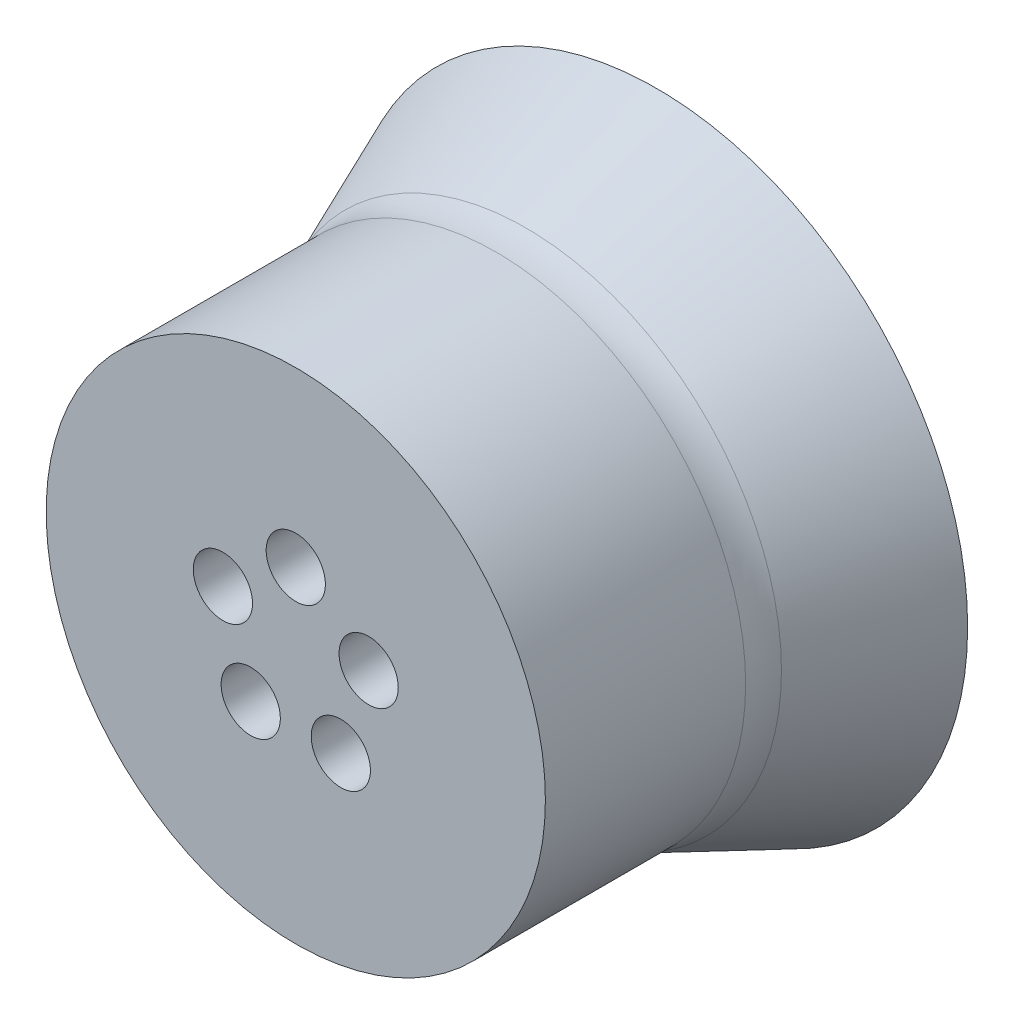
SolidWorks part; units mm, degrees
ref_plane "Front Plane" through (0, 0, 0) normal (0, 0, 1) x (1, 0, 0)
ref_plane "Top Plane" through (0, 0, 0) normal (0, 1, 0) x (1, 0, 0)
ref_plane "Right Plane" through (0, 0, 0) normal (1, 0, 0) x (0, 0, -1)
sketch "Sketch1" plane through (0, 0, 0) normal (0, 1, 0) x (1, 0, 0)
  line L1 (-23.1775, -34.925) -> (23.1775, -34.925) construction
  line L2 (34.925, -34.925) -> (34.925, 0)
  line L3 (34.925, 0) -> (37.465, 0)
  line L4 (37.465, 0) -> (46.6729, 16.7019)
  line L5 (46.6729, 16.7019) -> (38.371, -2.94)
  line L6 (37.465, -7.4107) -> (37.465, -37.465)
  line L7 (37.465, -37.465) -> (0, -37.465)
  line L8 (0, -37.465) -> (0, -34.925)
  line L9 (-23.1775, -34.925) -> (23.1775, -34.925) construction
  line L10 (20.0938, -31.8413) -> (-20.0938, -31.8413) construction
  line L11 (20.0938, -31.8413) -> (-20.0938, -31.8413) construction
  line L12 (-14.8504, -16.51) -> (14.8504, -16.51) construction
  line L13 (-17.9342, -19.5937) -> (17.9342, -19.5937) construction
  line L14 (-14.8504, -16.51) -> (14.8504, -16.51) construction
  line L15 (-17.9342, -19.5937) -> (17.9342, -19.5937) construction
  line L16 (23.1775, -34.925) -> (20.0938, -31.8413) construction
  line L17 (20.0938, -31.8413) -> (17.9342, -19.5937) construction
  line L18 (17.9342, -19.5937) -> (14.8504, -16.51) construction
  line L19 (14.8504, -16.51) -> (0, -16.51) construction
  line L20 (0, -16.51) -> (0, -34.925)
  line L21 (34.925, -34.925) -> (23.1775, -34.925)
  line L22 (22.8947, -34.925) -> (19.9077, -31.9381)
  line L23 (19.9077, -31.9381) -> (17.7482, -19.6906)
  line L24 (17.7482, -19.6906) -> (14.7676, -16.71)
  line L25 (14.7676, -16.71) -> (0, -16.71)
  line L26 (23.1775, -34.925) -> (22.8947, -34.925)
  line L27 (23.0361, -35.0664) -> (19.9077, -31.9381) construction
  arc A0 (38.371, -2.94) -> (37.465, -7.4107) centre (48.9484, -7.4107) ccw
  point P26 (0, 0)
  point P28 (0, 0)
  point P29 (0, 0)
  point P30 (0, 0)
  point P31 (0, 0)
  dimension "D1" = 2.54
  dimension "D3" = 11.4834
  dimension "D2" = 2.54
  dimension "D4" = 2.94
  dimension "D5" = 0.2
revolve "Revolve1" add sketch "Sketch1" angle 360 about L8 region at (16.725, 0, 25.2588)
sketch "Sketch3" plane through (0, 0, 37.465) normal (0, 0, 1) x (1, 0, 0)
  circle A0 centre (6.7595, -9.3037) radius 4.445
  circle A1 centre (10.9371, 3.5537) radius 1.8288
  circle A2 centre (10.9371, 3.5537) radius 1.8288
  circle A3 centre (0, 11.5) radius 1.8288
  circle A4 centre (0, 11.5) radius 1.8288
  circle A5 centre (-10.9371, 3.5537) radius 1.8288
  circle A6 centre (-10.9371, 3.5537) radius 1.8288
  circle A7 centre (-6.7595, -9.3037) radius 1.8288
  circle A8 centre (-6.7595, -9.3037) radius 1.8288
  circle A9 centre (6.7595, -9.3037) radius 1.8288
  circle A10 centre (6.7595, -9.3037) radius 1.8288
  circle A11 centre (-6.7595, -9.3037) radius 4.445
  circle A12 centre (-10.9371, 3.5537) radius 4.445
  circle A13 centre (0, 11.5) radius 4.445
  circle A14 centre (10.9371, 3.5537) radius 4.445
  dimension "D6" = 8.89
  dimension "D1" = 0
  dimension "D2" = 0
  dimension "D3" = 0
  dimension "D4" = 0
  dimension "D5" = 0
extrude "Cut-Extrude1" cut sketch "Sketch3" against normal through all contours A4 | A6 | A8 | A10 | A2
extrude "Cut-Extrude2" cut sketch "Sketch3<3>" against normal blind 12.7 contours A12 | A13 | A11 | A0 | A14
sketch "Sketch3<3>" plane through (0, 0, 37.465) normal (0, 0, 1) x (1, 0, 0) same geometry as "Sketch3"
fillet "Fillet1" radius 3.048 5 edges at (-2.3145, -9.3037, 24.765) (11.2045, -9.3037, 24.765) (15.3821, 3.5537, 24.765) (4.445, 11.5, 24.765) (-6.4921, 3.5537, 24.765)
